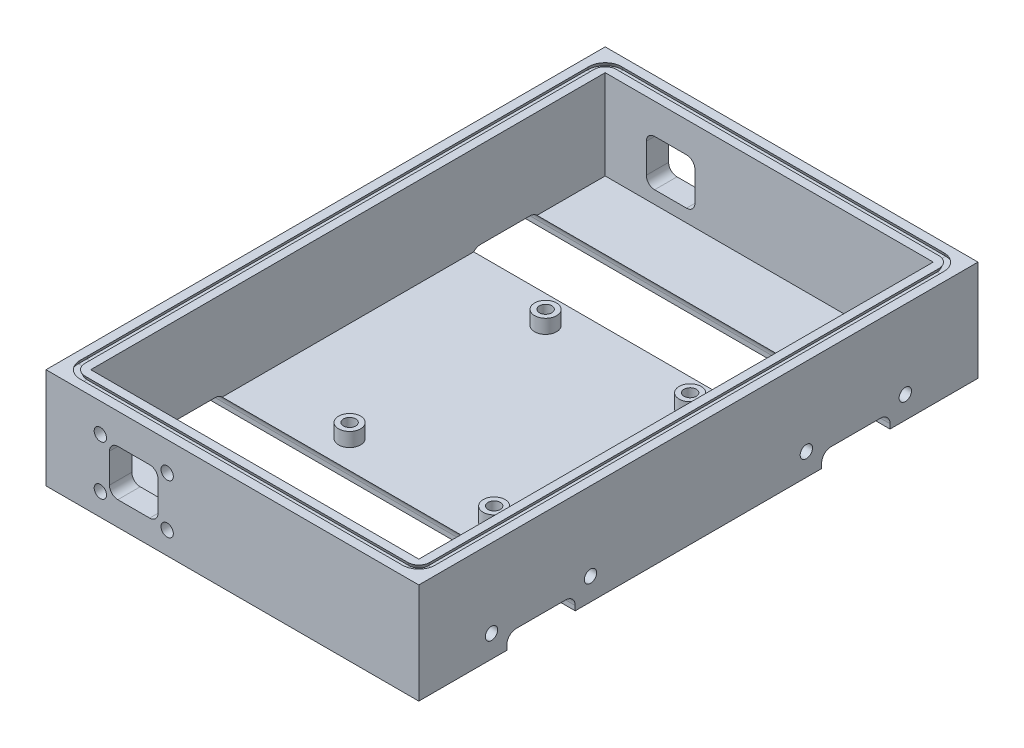
SolidWorks part; units mm, degrees
ref_plane "Front Plane" through (0, 0, 0) normal (0, 0, 1) x (1, 0, 0)
ref_plane "Top Plane" through (0, 0, 0) normal (0, 1, 0) x (1, 0, 0)
ref_plane "Right Plane" through (0, 0, 0) normal (1, 0, 0) x (0, 0, -1)
sketch "Sketch1" plane through (0, 0, 0) normal (0, 1, 0) x (1, 0, 0)
  line L1 (0, 0) -> (169.3418, 0)
  line L2 (0, 0) -> (0, 254)
  line L3 (0, 254) -> (169.3418, 254)
  line L4 (169.3418, 0) -> (169.3418, 254)
  dimension "D1" = 169.3418
  dimension "D2" = 254
extrude "Boss-Extrude1" add sketch "Sketch1" along normal blind 45.72
sketch "12 pin hole" [suppressed] plane through (254, 0, 0) normal (1, 0, 0) x (0, 0, -1)
  line L8 (50.8, 10.16) -> (95.758, 10.16) construction
  line L9 (50.8, 10.16) -> (50.8, 34.036) construction
  line L10 (50.8, 34.036) -> (95.758, 34.036) construction
  line L11 (95.758, 10.16) -> (95.758, 34.036) construction
  line L12 (55.7357, 28.956) -> (54.2925, 28.956)
  line L13 (52.7685, 27.432) -> (52.7685, 16.764)
  line L14 (54.2925, 15.24) -> (55.7357, 15.24)
  line L16 (90.087, 29.972) -> (92.2655, 29.972)
  line L17 (93.7895, 28.448) -> (93.7895, 15.748)
  line L18 (92.2655, 14.224) -> (90.087, 14.224)
  line L21 (62.4205, 25.654) -> (84.1375, 25.654) construction
  line L22 (62.4205, 25.654) -> (62.4205, 18.542) construction
  line L23 (62.4205, 18.542) -> (84.1375, 18.542) construction
  line L24 (84.1375, 25.654) -> (84.1375, 18.542) construction
  line L25 (62.4205, 32.7152) -> (84.1375, 32.7152)
  line L26 (62.4205, 11.4808) -> (84.1375, 11.4808)
  line L27 (52.7685, 22.098) -> (50.8, 22.098) construction
  line L28 (93.7895, 22.098) -> (95.758, 22.098) construction
  arc A4 (62.4205, 32.7152) -> (56.3868, 29.3222) centre (62.4205, 25.654) ccw
  arc A5 (89.5075, 30.2392) -> (84.1375, 32.7152) centre (84.1375, 25.654) ccw
  arc A6 (62.4205, 11.4808) -> (56.3868, 14.8738) centre (62.4205, 18.542) cw
  arc A7 (89.5075, 13.9568) -> (84.1375, 11.4808) centre (84.1375, 18.542) cw
  arc A8 (90.087, 29.972) -> (89.5075, 30.2392) centre (90.087, 30.734) cw
  arc A9 (90.087, 14.224) -> (89.5075, 13.9568) centre (90.087, 13.462) ccw
  arc A10 (55.7357, 15.24) -> (56.3868, 14.8738) centre (55.7357, 14.478) cw
  arc A11 (55.7357, 28.956) -> (56.3868, 29.3222) centre (55.7357, 29.718) ccw
  arc A12 (92.2655, 29.972) -> (93.7895, 28.448) centre (92.2655, 28.448) cw
  arc A13 (93.7895, 15.748) -> (92.2655, 14.224) centre (92.2655, 15.748) cw
  arc A14 (52.7685, 16.764) -> (54.2925, 15.24) centre (54.2925, 16.764) ccw
  arc A15 (54.2925, 28.956) -> (52.7685, 27.432) centre (54.2925, 27.432) ccw
  point P25 (50.8, 22.098)
  point P28 (52.7685, 22.098)
  point P29 (93.7895, 22.098)
  point P34 (62.4205, 22.098)
  point P35 (84.1375, 22.098)
  point P44 (73.279, 10.16)
  point P46 (73.279, 11.4808)
  point P59 (93.7895, 29.972)
  point P62 (93.7895, 14.224)
  point P65 (52.7685, 15.24)
  point P68 (52.7685, 28.956)
  dimension "D4" = 41.021
  dimension "D5" = 15.748
  dimension "D11" = 7.0612
  dimension "D12" = 0.762
  dimension "D13" = 1.524
  dimension "D1" = 44.958
  dimension "D2" = 23.876
  dimension "D8" = 13.716
  dimension "D9" = 21.2344
  dimension "D10" = 21.717
sketch "Sketch2" plane through (0, 45.72, 0) normal (0, 1, 0) x (1, 0, 0)
  line L0 (0, 254) -> (0, 0) construction
  line L1 (10.16, 10.16) -> (159.1818, 10.16)
  line L2 (10.16, 10.16) -> (10.16, 243.84)
  line L3 (10.16, 243.84) -> (159.1818, 243.84)
  line L4 (159.1818, 10.16) -> (159.1818, 243.84)
  line L5 (169.3418, 254) -> (0, 254) construction
  line L6 (169.3418, 0) -> (169.3418, 254) construction
  line L7 (0, 0) -> (169.3418, 0) construction
  dimension "D1" = 10.16
  dimension "D2" = 10.16
  dimension "D3" = 10.16
  dimension "D4" = 10.16
extrude "Cut-Extrude1" cut sketch "Sketch2" against normal blind 40.64
ref_plane "Plane1" through (0, 45.72, 0) normal (0, 1, 0) x (1, 0, 0)
sketch "Sketch3" plane through (0, 45.72, 0) normal (0, 1, 0) x (1, 0, 0)
  line L4 (6.35, 11.43) -> (6.35, 242.57)
  line L5 (159.1818, 243.84) -> (10.16, 243.84) construction
  line L6 (10.16, 243.84) -> (10.16, 10.16) construction
  line L7 (159.1818, 10.16) -> (159.1818, 243.84) construction
  line L8 (10.16, 10.16) -> (159.1818, 10.16) construction
  line L13 (11.43, 247.65) -> (157.9118, 247.65)
  line L14 (162.9918, 242.57) -> (162.9918, 11.43)
  line L15 (157.9118, 6.35) -> (11.43, 6.35)
  arc A0 (6.35, 242.57) -> (11.43, 247.65) centre (11.43, 242.57) cw
  arc A1 (157.9118, 247.65) -> (162.9918, 242.57) centre (157.9118, 242.57) cw
  arc A2 (162.9918, 11.43) -> (157.9118, 6.35) centre (157.9118, 11.43) cw
  arc A3 (11.43, 6.35) -> (6.35, 11.43) centre (11.43, 11.43) cw
  dimension "D5" = 5.08
  dimension "D1" = 3.81
  dimension "D2" = 3.81
  dimension "D3" = 3.81
  dimension "D4" = 3.81
ref_plane "Plane2" through (0, 0, 0) normal (0, 0, 1) x (1, 0, 0)
ref_plane "Plane3" through (0, 0, -15.24) normal (0, 0, 1) x (1, 0, 0)
sketch "Sketch4" plane through (0, 0, -15.24) normal (0, 0, 1) x (1, 0, 0)
  line L0 (4.064, 45.72) -> (3.2724, 43.942)
  line L1 (6.35, 45.72) -> (7.1416, 43.942)
  line L2 (3.2724, 43.942) -> (7.1416, 43.942)
  line L5 (4.064, 45.72) -> (6.35, 45.72)
  dimension "D1" = 1.778
  dimension "D2" = 2.286
  dimension "D3" = 66
  dimension "D4" = 66
sweep "Cut-Sweep2" cut profiles "Sketch4" path "Sketch3"
sketch "Sketch13" plane through (169.3418, 0, 0) normal (1, 0, 0) x (0, 0, -1)
  line L0 (33.02, 10.16) -> (33.02, 0) construction
  line L1 (0, 0) -> (254, 0) construction
  line L2 (33.02, 10.16) -> (0, 10.16) construction
  line L3 (0, 45.72) -> (0, 0) construction
  line L4 (220.98, 0) -> (220.98, 10.16) construction
  line L5 (220.98, 10.16) -> (254, 10.16) construction
  line L6 (254, 45.72) -> (254, 0) construction
  line B0 (48.5902, -10.7823) -> (48.5902, -12.4587)
  line B1 (33.02, 10.16) -> (77.978, 10.16) construction
  line B2 (33.02, 10.16) -> (33.02, -13.716) construction
  line B3 (33.02, -13.716) -> (77.978, -13.716) construction
  line B4 (77.978, 10.16) -> (77.978, -13.716) construction
  line B5 (44.2976, 6.4643) -> (66.7004, 6.4643)
  line B6 (39.9542, 2.1209) -> (39.9542, -5.6769)
  line B7 (44.2976, -10.0203) -> (47.8282, -10.0203)
  line B8 (71.0438, 2.1209) -> (71.0438, -5.6769)
  line B9 (39.9542, 6.4643) -> (71.0438, -10.0203) construction
  line B10 (39.9542, -10.0203) -> (71.0438, 6.4643) construction
  line B11 (49.3522, -13.2207) -> (61.6458, -13.2207)
  line B12 (62.4078, -12.4587) -> (62.4078, -10.7823)
  line B13 (63.1698, -10.0203) -> (66.7004, -10.0203)
  arc B14 (66.7004, -10.0203) -> (71.0438, -5.6769) centre (66.7004, -5.6769) ccw
  arc B15 (39.9542, -5.6769) -> (44.2976, -10.0203) centre (44.2976, -5.6769) ccw
  arc B16 (66.7004, 6.4643) -> (71.0438, 2.1209) centre (66.7004, 2.1209) cw
  arc B17 (44.2976, 6.4643) -> (39.9542, 2.1209) centre (44.2976, 2.1209) ccw
  arc B18 (62.4078, -10.7823) -> (63.1698, -10.0203) centre (63.1698, -10.7823) cw
  arc B19 (61.6458, -13.2207) -> (62.4078, -12.4587) centre (61.6458, -12.4587) ccw
  arc B20 (48.5902, -12.4587) -> (49.3522, -13.2207) centre (49.3522, -12.4587) ccw
  arc B21 (48.5902, -10.7823) -> (47.8282, -10.0203) centre (47.8282, -10.7823) ccw
  line B22 (191.5922, -10.7823) -> (191.5922, -12.4587)
  line B23 (176.022, 10.16) -> (220.98, 10.16) construction
  line B24 (176.022, 10.16) -> (176.022, -13.716) construction
  line B25 (176.022, -13.716) -> (220.98, -13.716) construction
  line B26 (220.98, 10.16) -> (220.98, -13.716) construction
  line B27 (187.2996, 6.4643) -> (209.7024, 6.4643)
  line B28 (182.9562, 2.1209) -> (182.9562, -5.6769)
  line B29 (187.2996, -10.0203) -> (190.8302, -10.0203)
  line B30 (214.0458, 2.1209) -> (214.0458, -5.6769)
  line B31 (182.9562, 6.4643) -> (214.0458, -10.0203) construction
  line B32 (182.9562, -10.0203) -> (214.0458, 6.4643) construction
  line B33 (192.3542, -13.2207) -> (204.6478, -13.2207)
  line B34 (205.4098, -12.4587) -> (205.4098, -10.7823)
  line B35 (206.1718, -10.0203) -> (209.7024, -10.0203)
  arc B36 (209.7024, -10.0203) -> (214.0458, -5.6769) centre (209.7024, -5.6769) ccw
  arc B37 (182.9562, -5.6769) -> (187.2996, -10.0203) centre (187.2996, -5.6769) ccw
  arc B38 (209.7024, 6.4643) -> (214.0458, 2.1209) centre (209.7024, 2.1209) cw
  arc B39 (187.2996, 6.4643) -> (182.9562, 2.1209) centre (187.2996, 2.1209) ccw
  arc B40 (205.4098, -10.7823) -> (206.1718, -10.0203) centre (206.1718, -10.7823) cw
  arc B41 (204.6478, -13.2207) -> (205.4098, -12.4587) centre (204.6478, -12.4587) ccw
  arc B42 (191.5922, -12.4587) -> (192.3542, -13.2207) centre (192.3542, -12.4587) ccw
  arc B43 (191.5922, -10.7823) -> (190.8302, -10.0203) centre (190.8302, -10.7823) ccw
  dimension "D1" = 33.02
  dimension "D2" = 10.16
sketch_block_instance "Block7-3"
sketch_block "Block7" parameters "D6"=4.3434, "D7"=0.762, "D1"=44.958, "D2"=23.876, "D3"=31.0896, "D4"=16.4846, "D5"=19.685
sketch_block_instance "Block7-4"
extrude "Cut-Extrude10" cut sketch "Sketch13" against normal up to next
sketch "12 pin mount" plane through (169.3418, 0, 0) normal (1, 0, 0) x (0, 0, -1)
  circle A0 centre (77.978, -13.716) radius 2.8
  circle A1 centre (77.978, 10.16) radius 2.8
  circle A2 centre (33.02, 10.16) radius 2.8
  circle A3 centre (33.02, -13.716) radius 2.8
  circle A4 centre (176.022, -13.716) radius 2.8
  circle A5 centre (220.98, -13.716) radius 2.8
  circle A6 centre (220.98, 10.16) radius 2.8
  circle A7 centre (176.022, 10.16) radius 2.8
  dimension "D1" = 5.6
extrude "Cut-Extrude3" cut sketch "12 pin mount" against normal blind 5.5
sketch "4 pin connector" plane through (0, 0, 0) normal (0, 0, 1) x (1, 0, 0)
  line L0 (55.0418, 0) -> (55.0418, 10.16) construction
  line L1 (0, 0) -> (169.3418, 0) construction
  line L2 (55.0418, 10.16) -> (169.3418, 10.16) construction
  line L3 (169.3418, 45.72) -> (169.3418, 0) construction
  line L5 (24.6888, 32.6136) -> (55.0418, 32.6136) construction
  line L6 (24.6888, 32.6136) -> (24.6888, 10.16) construction
  line L7 (24.6888, 10.16) -> (55.0418, 10.16) construction
  line L8 (55.0418, 32.6136) -> (55.0418, 10.16) construction
  line L9 (32.6263, 31.877) -> (47.1043, 31.877)
  line L10 (28.8163, 28.067) -> (28.8163, 14.7066)
  line L11 (32.6263, 10.8966) -> (47.1043, 10.8966)
  line L12 (50.9143, 28.067) -> (50.9143, 14.7066)
  line L13 (39.8653, 10.8966) -> (39.8653, 31.877) construction
  line L14 (28.8163, 21.3868) -> (50.9143, 21.3868) construction
  arc A0 (47.1043, 31.877) -> (50.9143, 28.067) centre (47.1043, 28.067) cw
  arc A1 (47.1043, 10.8966) -> (50.9143, 14.7066) centre (47.1043, 14.7066) ccw
  arc A2 (28.8163, 14.7066) -> (32.6263, 10.8966) centre (32.6263, 14.7066) ccw
  arc A3 (32.6263, 31.877) -> (28.8163, 28.067) centre (32.6263, 28.067) ccw
  point P4 (39.8653, 21.3868)
  point P12 (39.8653, 10.16)
  point P15 (55.0418, 21.3868)
  point P20 (50.9143, 31.877)
  point P24 (50.9143, 10.8966)
  point P29 (28.8163, 31.877)
  dimension "D1" = 22.098
  dimension "D7" = 3.81
  dimension "D2" = 22.4536
  dimension "D3" = 30.353
  dimension "D4" = 10.16
  dimension "D5" = 114.3
  dimension "D6" = 20.9804
extrude "Cut-Extrude5" cut sketch "4 pin connector" against normal up to next
extrude "Cut-Extrude6" cut sketch "Sketch5<2>" along normal up to next from surface starting at face at (84.6709, 22.86, -254)
sketch "Sketch5<2>" plane through (0, 0, 0) normal (0, 0, 1) x (1, 0, 0) same geometry as "4 pin connector"
sketch "Sketch6" plane through (0, 0, 0) normal (0, 0, 1) x (1, 0, 0)
  circle A0 centre (55.0418, 32.6136) radius 2.8
  circle A1 centre (55.0418, 10.16) radius 2.8
  circle A2 centre (24.6888, 10.16) radius 2.8
  circle A3 centre (24.6888, 32.6136) radius 2.8
  dimension "D1" = 5.6
extrude "Cut-Extrude7" cut sketch "Sketch6" against normal blind 5.5
extrude "Cut-Extrude8" cut sketch "Sketch6<2>" along normal blind 5.5 from surface starting at face at (39.8653, 21.3868, -254)
sketch "Sketch6<2>" plane through (0, 0, 0) normal (0, 0, 1) x (1, 0, 0) same geometry as "Sketch6"
sketch "Sketch7" plane through (0, 5.08, 0) normal (0, 1, 0) x (1, 0, 0)
  line L0 (121.0818, 127) -> (159.1818, 127) construction
  line L1 (159.1818, 10.16) -> (159.1818, 41.1182) construction
  line L2 (159.1818, 10.16) -> (159.1818, 243.84) construction
  line L5 (121.0818, 82.485) -> (55.4218, 82.485) construction
  line L6 (121.0818, 82.485) -> (121.0818, 171.515) construction
  line L7 (121.0818, 171.515) -> (55.4218, 171.515) construction
  line L8 (55.4218, 82.485) -> (55.4218, 171.515) construction
  circle A0 centre (55.4218, 82.485) radius 5
  circle A1 centre (121.0818, 82.485) radius 5
  circle A2 centre (121.0818, 171.515) radius 5
  circle A3 centre (55.4218, 171.515) radius 5
  dimension "D1" = 10
  dimension "D2" = 89.03
  dimension "D3" = 65.66
  dimension "D4" = 38.1
sketch "Sketch8" plane through (0, 5.08, 0) normal (0, 1, 0) x (1, 0, 0)
  circle A0 centre (55.4218, 171.515) radius 2.8
  circle A1 centre (121.0818, 171.515) radius 2.8
  circle A2 centre (121.0818, 82.485) radius 2.8
  circle A3 centre (55.4218, 82.485) radius 2.8
  dimension "D1" = 5.6
extrude "Boss-Extrude2" add sketch "Sketch7" along normal blind 6.35
extrude "Cut-Extrude9" cut sketch "Sketch8" against normal blind 5.5 from surface starting at face at (121.0818, 11.43, -77.485)
equation "\"M4 insert  width\"= 5.6mm"
equation "\"M4 insert  depth\"= 5.5mm"
equation "\"depth\"=0.1"
